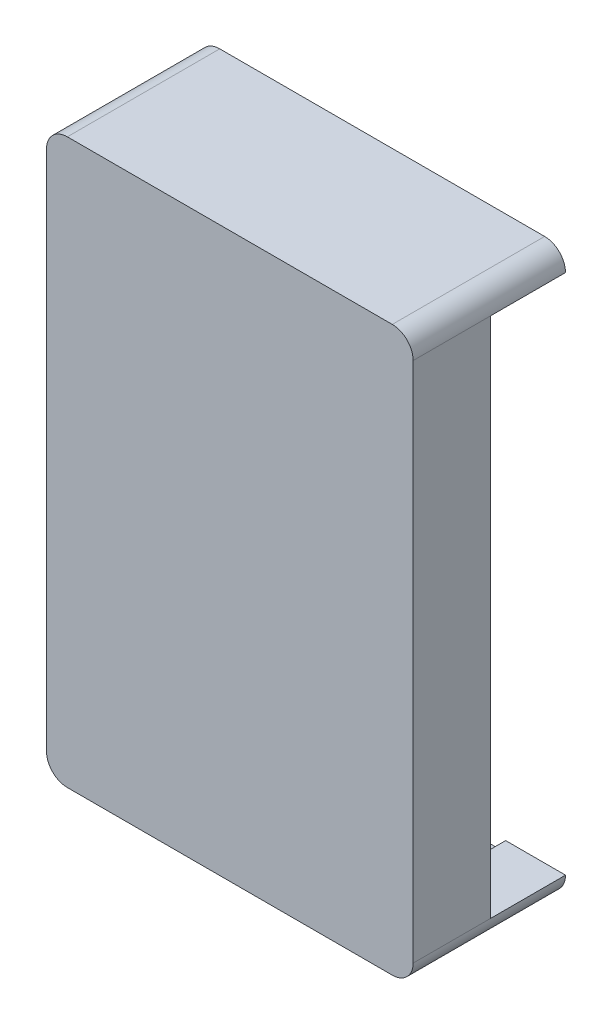
SolidWorks part; units mm, degrees
note: The reader was unsure of these and kept them because the rebuilt part matched: shared geometry of "Sketch1<3>".
ref_plane "Front Plane" through (0, 0, 0) normal (0, 0, 1) x (1, 0, 0)
ref_plane "Top Plane" through (0, 0, 0) normal (0, 1, 0) x (1, 0, 0)
ref_plane "Right Plane" through (0, 0, 0) normal (1, 0, 0) x (0, 0, -1)
sketch "Sketch1" plane through (0, 0, 0) normal (0, 1, 0) x (1, 0, 0)
  line L0 (26.35, 0) -> (26.35, 11.15)
  line L1 (0, 0) -> (52.7, 0)
  line L2 (0, 0) -> (0, 21.9)
  line L4 (52.7, 0) -> (52.7, 21.9)
  line L5 (26.35, 11.15) -> (29.35, 11.15)
  line L6 (26.35, 11.15) -> (23.35, 11.15)
  line L7 (12.6, 0.4) -> (12.6, 0)
  line L8 (1.85, 11.15) -> (0, 11.15)
  line L9 (50.85, 11.15) -> (52.7, 11.15)
  line L10 (0, 21.9) -> (52.7, 21.9)
  circle A0 centre (12.6, 11.15) radius 10.75
  circle A1 centre (40.1, 11.15) radius 10.75
  dimension "D2" = 21.5
  dimension "D3" = 21.5
  dimension "D1" = 52.7
  dimension "D4" = 3
  dimension "D5" = 3
  dimension "D6" = 0.4
extrude "Boss-Extrude1" add sketch "Sketch1" along normal blind 75 contours A0 L8 L2 L1 L7 | A0 L7 L1 L0 L6 | A1 L5 L0 L1 L4 L9
extrude "Boss-Extrude2" add sketch "Sketch1<3>" against normal blind 3 contours A1 L9 L4 L10 | A1 L5 L0 L1 L4 L9 | A1 | A1 L10 A0 L6 L5 | A0 L7 L1 L0 L6 | A0 | A0 L8 L2 L1 L7 | A0 L10 L2 L8
sketch "Sketch1<3>" plane through (0, 0, 0) normal (0, 1, 0) x (1, 0, 0) same geometry as "Sketch1"
sketch "Sketch4" plane through (0, 0, -21.9) normal (0, 0, -1) x (-1, 0, 0)
  line L0 (0, -0.95) -> (-12.6, -0.95) construction
  line L1 (0, -3) -> (0, 0) construction
  line L2 (0, 0) -> (-52.7, 0) construction
  line L3 (-6.475, -1.5) -> (-18.725, -1.5)
  line L4 (-6.475, -1.5) -> (-6.475, -0.4)
  line L5 (-6.475, -0.4) -> (-18.725, -0.4)
  line L6 (-18.725, -1.5) -> (-18.725, -0.4)
  line L7 (-6.475, -1.5) -> (-18.725, -0.4) construction
  line L8 (-6.475, -0.4) -> (-18.725, -1.5) construction
  line L9 (-12.6, -0.95) -> (-12.6, 0)
  line L10 (-12.6, 0) -> (-8.6, 0)
  line L11 (-8.6, 0) -> (-8.6, -0.4)
  line L12 (-12.6, 0) -> (-16.6, 0)
  line L13 (-16.6, 0) -> (-16.6, -0.4)
  dimension "D1" = 1.1
  dimension "D2" = 12.25
  dimension "D3" = 12.6
  dimension "D4" = 0.4
  dimension "D5" = 4
  dimension "D6" = 4
extrude "Cut-Extrude1" cut sketch "Sketch4" against normal blind 16.75
ref_plane "Plane2" through (26.35, 0, 0) normal (1, 0, 0) x (0, 0, -1)
ref_plane "Plane3" through (0, 37.5, 0) normal (0, 1, 0) x (1, 0, 0)
mirror "Mirror2" about plane through (26.35, 0, 0) normal (1, 0, 0) of "Cut-Extrude1"
mirror "Mirror3" about plane through (0, 37.5, 0) normal (0, 1, 0) of "Boss-Extrude2", "Mirror2", "Cut-Extrude1"
sketch "Sketch5" plane through (0, 0, -21.9) normal (0, 0, -1) x (-1, 0, 0)
  line L1 (-33.975, 76.5) -> (-18.725, 76.5)
  line L2 (-33.975, 76.5) -> (-33.975, 75.4)
  line L3 (-33.975, 75.4) -> (-18.725, 75.4)
  line L4 (-18.725, 76.5) -> (-18.725, 75.4)
extrude "Cut-Extrude2" cut sketch "Sketch5" against normal blind 2
fillet "Fillet1" radius 3 4 edges at (0, 78, -10.95) (52.7, 78, -10.95) (52.7, -3, -10.95) (0, -3, -10.95)
